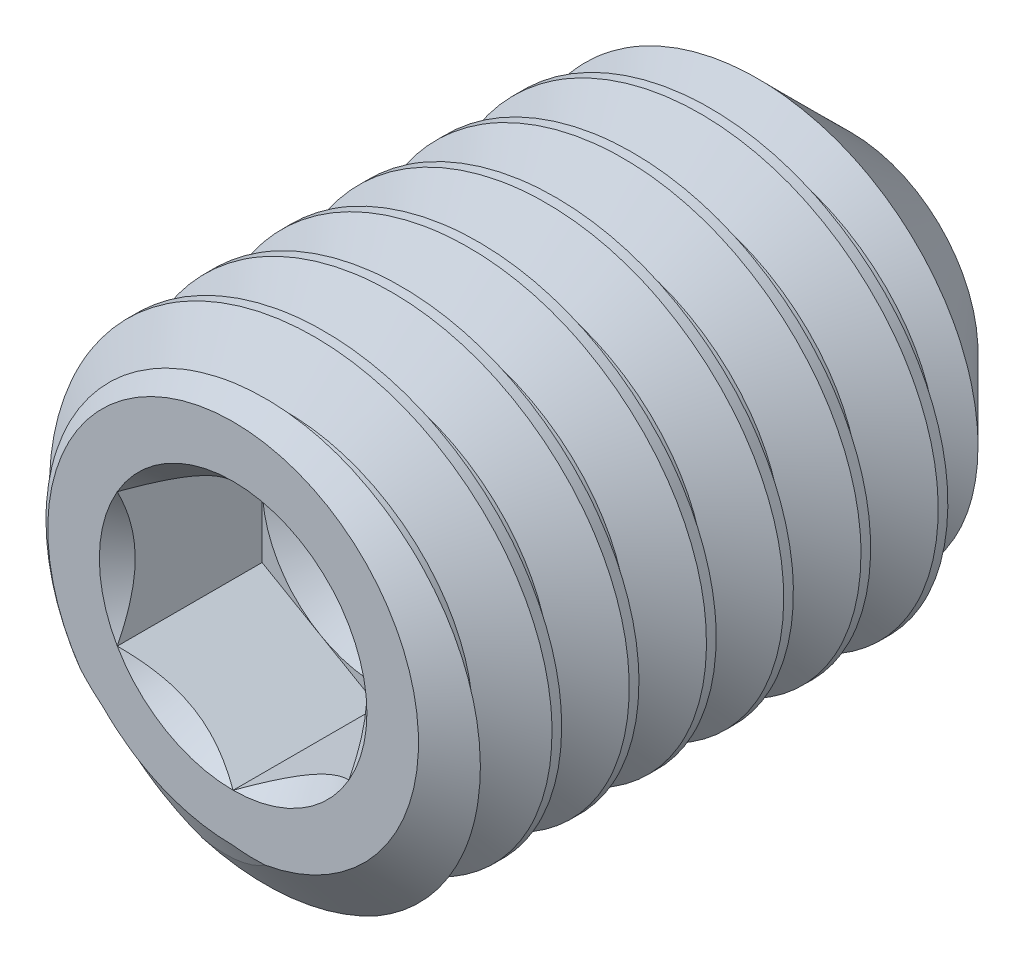
SolidWorks part; units mm, degrees
ref_plane "Front" through (0, 0, 0) normal (0, 0, 1) x (1, 0, 0)
ref_plane "Top" through (0, 0, 0) normal (0, 1, 0) x (1, 0, 0)
ref_plane "Right" through (0, 0, 0) normal (1, 0, 0) x (0, 0, -1)
sketch "Sketch22" plane through (0, 0, 0) normal (1, 0, 0) x (0, 0, -1)
  line L0 (-1.7531, 0) -> (-1.7531, 1.2)
  line L1 (-1.7531, 1.2) -> (-1.543, 1.5)
  line L2 (-1.543, 1.5) -> (1.5689, 1.5)
  line L3 (1.5689, 1.5) -> (2.2469, 0.8219)
  line L4 (2.2469, 0.8219) -> (1.7531, 0)
  line L5 (1.7531, 0) -> (-1.7531, 0)
  line L6 (1.7531, 0) -> (2.2469, 0) construction
  line L7 (2.2469, 0) -> (2.2469, 0.8219) construction
  line L8 (2.2469, -0.8219) -> (1.7531, 0) construction
  line L9 (-1.543, -1.5) -> (1.5689, -1.5) construction
  dimension "Dia" = 3
  dimension "Length" = 4
  dimension "D3" = 35
  dimension "D5" = 118
  dimension "D6" = 45
  dimension "D7" = 2.4
revolve "Revolve1" add sketch "Sketch22" angle 360 about L6
ref_plane "Plane1" through (0, 0, -2.2469) normal (0, 0, 1) x (1, 0, 0)
sketch "Sketch27" plane through (0, 0, -2.2469) normal (0, 0, 1) x (1, 0, 0)
  circle A0 centre (0, 0) radius 1.5 construction
  circle A1 centre (0, 0) radius 1.5
curve "Helix/Spiral1" pitch 0.5 height 4.5 turns 9
sketch "Sketch28" plane through (0, 0, 0) normal (1, 0, 0) x (0, 0, -1)
  line L0 (2.2469, 1.5) -> (2.6844, 1.5)
  line L1 (2.6844, 1.5) -> (2.4969, 1.1752)
  line L2 (2.4969, 1.1752) -> (2.4344, 1.1752)
  line L3 (2.4344, 1.1752) -> (2.2469, 1.5)
  line L4 (2.3407, 1.3376) -> (2.5907, 1.3376) construction
  line L6 (-1.543, 1.5) -> (1.5689, 1.5) construction
  dimension "D1" = 0.0625
  dimension "D3" = 60
  dimension "D2" = 0.25
sweep "Cut-Sweep2" cut profiles "Sketch28" path "Helix/Spiral1"
sketch "Sketch23" plane through (0, 0, 1.7531) normal (0, 0, 1) x (1, 0, 0)
  line L1 (0, 0.866) -> (-0.75, 0.433)
  line L2 (-0.75, 0.433) -> (-0.75, -0.433)
  line L3 (-0.75, -0.433) -> (0, -0.866)
  line L4 (0, -0.866) -> (0.75, -0.433)
  line L5 (0.75, -0.433) -> (0.75, 0.433)
  line L6 (0.75, 0.433) -> (0, 0.866)
  circle A0 centre (0, 0) radius 0.75 construction
  dimension "Hex" = 1.5
extrude "Cut-Extrude10" cut sketch "Sketch23" against normal blind 0.9375
sketch "Sketch24" plane through (0, 0, 1.7531) normal (0, 0, 1) x (1, 0, 0)
  circle A0 centre (0, 0) radius 0.866
extrude "Cut-Extrude11" cut sketch "Sketch24" against normal through all draft 45
sketch "Sketch26" plane through (0, 0, 0.8156) normal (0, 0, 1) x (1, 0, 0)
  circle A0 centre (0, 0) radius 0.75 construction
  circle A1 centre (0, 0) radius 0.75
extrude "Cut-Extrude12" cut sketch "Sketch26" against normal through all draft 60
sketch "Sketch30" plane through (0, 0, 0) normal (1, 0, 0) x (0, 0, -1)
  line L0 (-1.543, 1.5) -> (1.5689, 1.5) construction
  line L1 (-1.7531, 0) -> (-1.7531, 1.2) construction
  line L2 (2.2469, 0) -> (2.2469, 0.8219) construction
  line L3 (-1.543, -1.5) -> (1.5689, -1.5) construction
  point P0 (-1.7531, 1.5)
  point P1 (2.2469, 1.5)
  point P2 (2.2469, -1.5)
  point P11 (1.4969, -1.5)
  dimension "D1" = 0.75
sketch "Sketch31" plane through (0, 0, 0) normal (1, 0, 0) x (0, 0, -1)
  line L2 (1.7531, 0) -> (2.2469, -0.8219)
  line L3 (2.2469, 0.8219) -> (1.7531, 0)
equation "\"D7@Sketch22\"=\"Dia@Sketch22\"*.8"
equation "\"D1@Sketch28\" = \"D4@Helix/Spiral1\" * .125"
equation "\"D2@Sketch28\" = \"D4@Helix/Spiral1\" * .5"
equation "\"D3@Helix/Spiral1\" = \"Length@Sketch22\" + \"D4@Helix/Spiral1\""
equation "\"D1@Sketch30\" = \"D4@Helix/Spiral1\" * 1.5"
equation "\"hex Depth@Cut-Extrude10\" = \"Hex@Sketch23\" * .625"
